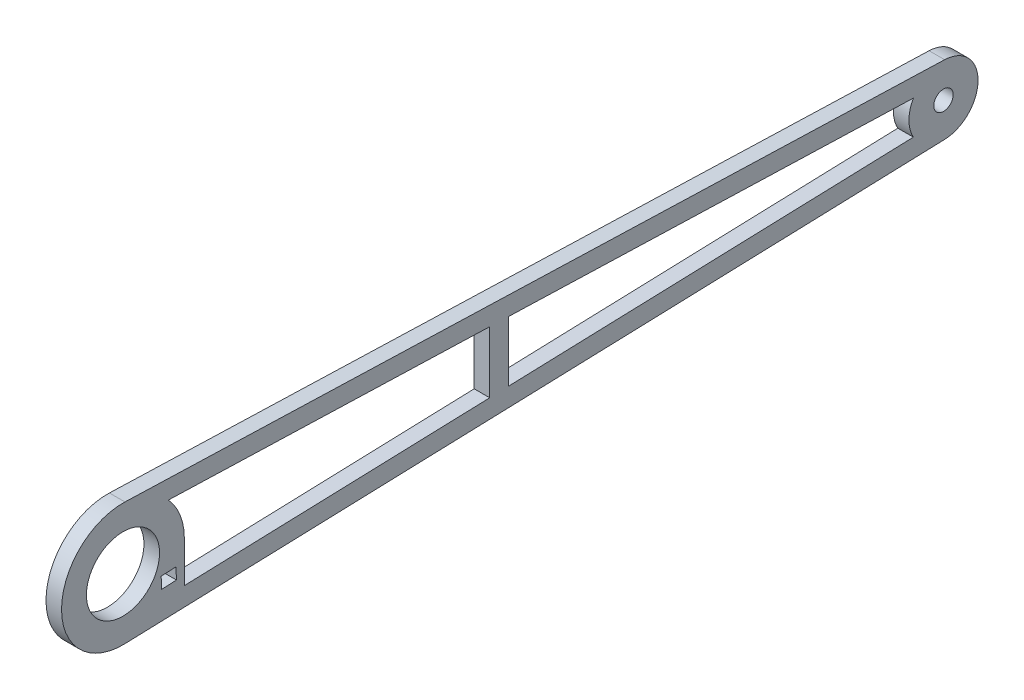
SolidWorks part; units mm, degrees
material "Delrin"
ref_plane "Front Plane" through (0, 0, 0) normal (0, 0, 1) x (1, 0, 0)
ref_plane "Top Plane" through (0, 0, 0) normal (0, 1, 0) x (1, 0, 0)
ref_plane "Right Plane" through (0, 0, 0) normal (1, 0, 0) x (0, 0, -1)
sketch "Sketch1" plane through (0, 0, 0) normal (1, 0, 0) x (0, 0, -1)
  line L0 (0.2053, 6.2704) -> (83.9355, 3.5287)
  line L1 (0, -6.2772) -> (83.9355, -3.5287)
  line L2 (-1000, 0) -> (49000, 0) construction
  line L3 (4.6432, 4.2191) -> (80.7408, 1.7273)
  line L4 (4.6432, -4.2191) -> (80.7408, -1.7273)
  line L5 (0.143, 4.3665) -> (83.8732, 1.6247) construction
  line L6 (-0.0623, -4.3732) -> (83.8732, -1.6247) construction
  line L7 (83.82, -1000) -> (83.82, 49000) construction
  line L8 (5.506, -3.304) -> (5.447, -2.0354) construction
  line L9 (5.447, -2.0354) -> (3.8612, -2.1091) construction
  line L10 (3.9202, -3.3777) -> (3.8612, -2.1091) construction
  line L11 (5.506, -3.304) -> (3.9202, -3.3777) construction
  line L12 (5.506, -3.304) -> (5.447, -2.0354) construction
  line L13 (5.447, -2.0354) -> (3.8612, -2.1091) construction
  line L14 (3.9202, -3.3777) -> (3.8612, -2.1091) construction
  line L15 (5.506, -3.304) -> (3.9202, -3.3777) construction
  line L16 (6.2738, 0) -> (6.2738, -4.1657)
  line L17 (39.37, 3.082) -> (39.37, -3.082)
  line L18 (37.465, 3.1444) -> (37.465, -3.1444)
  line L19 (5.4107, -2.0752) -> (3.9011, -2.1454)
  line L20 (3.9565, -3.3379) -> (3.9011, -2.1454)
  line L21 (5.4661, -3.2678) -> (3.9565, -3.3379)
  line L22 (5.4661, -3.2678) -> (5.4107, -2.0752)
  circle A0 centre (0, 0) radius 3.7338
  circle A1 centre (0, 0) radius 6.2738
  circle A2 centre (83.82, 0) radius 0.9906
  circle A3 centre (83.82, 0) radius 3.5306
  circle A4 centre (83.82, 15.875) radius 1.016
  circle A5 centre (83.82, 15.875) radius 3.556
  dimension "D1" = 7.4676
  dimension "D2" = 2.54
  dimension "D3" = 1.9812
  dimension "D8" = 2.032
  dimension "D5" = 83.82
  dimension "D10" = 15.875
  dimension "D11" = 44.45
  dimension "D12" = 1.905
  dimension "D4" = 2.54
  dimension "D6" = 1.905
  dimension "D7" = 1.905
  dimension "D9" = 2.54
  dimension "D13" = 0.0381
extrude "Boss-Extrude1" add sketch "Sketch1" along normal blind 1.5875 contours A1 L2 A0 | A1 L2 A3 L0 | L2 A1 L1 A3 | A3 L2 A2 | A1 L4 L16 | L3 L18 L4 L17 region at (0, 3.9454, -42.4708) region at (0, 5.5338, -2.5579) region at (0, 2.3859, -86.2853) region at (0, -3.9454, -42.4708) region at (0, 0, -38.4143) region at (0, -3.1728, -5.801)
sketch3d "3DSketch1"
  line L0 (0, 6.2704, -0.2053) -> (0, 3.5287, -83.9355) construction
  line L1 (0, 3.5649, -82.8294) -> (1.5875, 3.5649, -82.8294)
  line L2 (0, 3.5649, -82.8294) -> (0, -3.5649, -82.8294)
  line L3 (0, -3.5649, -82.8294) -> (1.5875, -3.5649, -82.8294)
  line L4 (1.5875, 3.5649, -82.8294) -> (1.5875, -3.5649, -82.8294)
  line L5 (1.5875, -6.2704, -0.2053) -> (1.5875, -3.5287, -83.9355) construction
